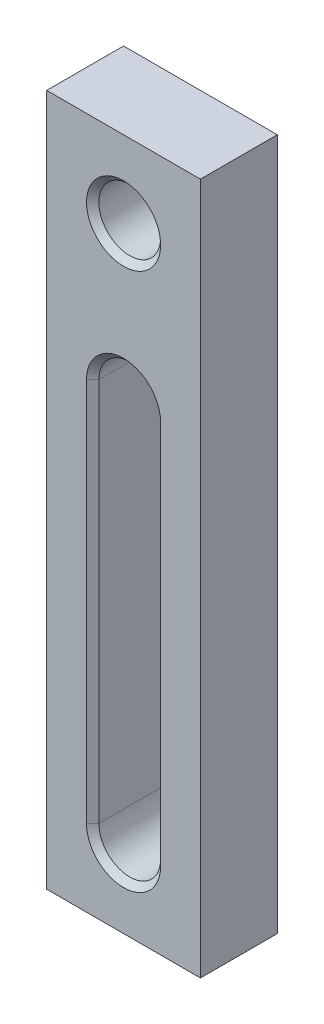
SolidWorks part; units mm, degrees
ref_plane "Спереди" through (0, 0, 0) normal (0, 0, 1) x (1, 0, 0)
ref_plane "Сверху" through (0, 0, 0) normal (0, 1, 0) x (1, 0, 0)
ref_plane "Справа" through (0, 0, 0) normal (1, 0, 0) x (0, 0, -1)
sketch "Эскиз1" plane through (0, 0, 0) normal (0, 0, 1) x (1, 0, 0)
  line L1 (0, 0) -> (50, 0)
  line L2 (0, 0) -> (0, 225)
  line L3 (0, 225) -> (50, 225)
  line L4 (50, 0) -> (50, 225)
  dimension "D1" = 50
  dimension "D2" = 225
extrude "Бобышка-Вытянуть1" add sketch "Эскиз1" along normal blind 25
sketch "Эскиз2" plane through (0, 0, 25) normal (0, 0, 1) x (1, 0, 0)
  line L1 (14.95, 25) -> (14.95, 150)
  line L2 (35.05, 25) -> (35.05, 150)
  line L3 (0, 225) -> (0, 0) construction
  line L4 (0, 0) -> (50, 0) construction
  arc A0 (14.95, 25) -> (35.05, 25) centre (25, 25) ccw
  arc A1 (14.95, 150) -> (35.05, 150) centre (25, 150) cw
  circle A2 centre (25, 200) radius 10.05
  point P7 (14.95, 87.5)
  point P10 (35.05, 87.5)
  point P14 (0, 0)
  point P15 (0, 0)
  point P16 (0, 0)
  dimension "D1" = 25
  dimension "D2" = 25
extrude "Вырез-Вытянуть1" cut sketch "Эскиз2" against normal through all
chamfer "Фаска1" distance 2 angle 45 10 edges at (14.95, 87.5, 0) (25, 14.95, 0) (25, 160.05, 0) (35.05, 87.5, 0) (35.05, 87.5, 25) (25, 160.05, 25) (25, 14.95, 25) (14.95, 87.5, 25) (35.05, 200, 0) (35.05, 200, 25)
